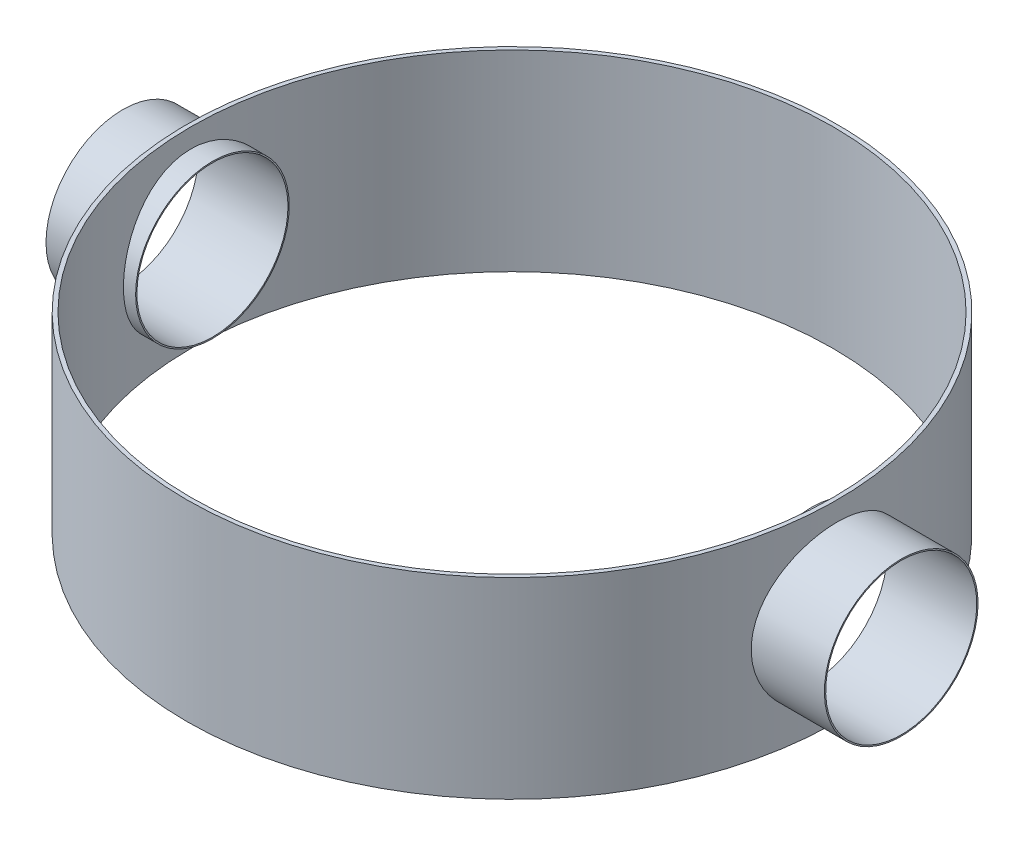
SolidWorks part; units mm, degrees
material "AISI 304"
ref_plane "Piano frontale" through (0, 0, 0) normal (0, 0, 1) x (1, 0, 0)
ref_plane "Piano superiore" through (0, 0, 0) normal (0, 1, 0) x (1, 0, 0)
ref_plane "Piano destro" through (0, 0, 0) normal (1, 0, 0) x (0, 0, -1)
sketch "Schizzo2" plane through (0, 0, 0) normal (0, 1, 0) x (1, 0, 0)
  circle A0 centre (0, 0) radius 254
extrude "Estrusione-Sottile1" add sketch "Schizzo2" along normal mid plane 150 thin thin type one direction reverse wall 3.2
sketch "Schizzo3" plane through (0, 0, 0) normal (0, 0, 1) x (1, 0, 0)
  line L2 (234, 0) -> (304, 0)
  point P6 (0, 0)
sweep "Sweep-Sottile2" add path "Schizzo3" circular profile diameter 120 parameters "D1"=1, "D3"=120
sketch "Schizzo26" plane through (304, 0, 0) normal (1, 0, 0) x (0, 0, -1)
  circle A0 centre (0, 0) radius 59 construction
  circle A1 centre (0, 0) radius 59
extrude "Taglio-Estrusione1" cut sketch "Schizzo26" against normal up to surface (558 mm away) up to face at (253.7187, -58.7977, 11.9513)
pattern_circular "RipetizioneCircolare1" count 2 every 180 about axis through (0, 75, 0) along (0, 1, 0) of "Sweep-Sottile2"
